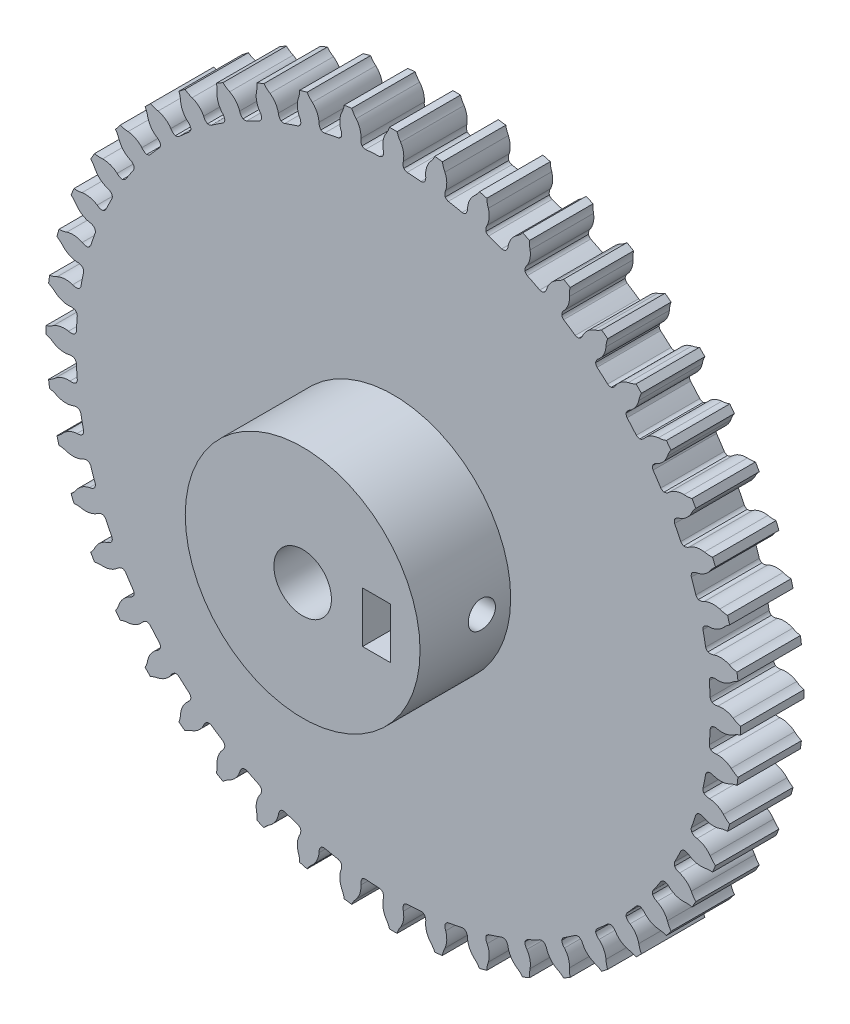
SolidWorks part; units mm, degrees
ref_plane "Front Plane" through (0, 0, 0) normal (0, 0, 1) x (1, 0, 0)
ref_plane "Top Plane" through (0, 0, 0) normal (0, 1, 0) x (1, 0, 0)
ref_plane "Right Plane" through (0, 0, 0) normal (1, 0, 0) x (0, 0, -1)
sketch "Sketch1" plane through (0, 0, 0) normal (0, 0, 1) x (1, 0, 0)
  line L0 (27.683, 56.4388) -> (28.5235, 56.4388)
  line L1 (28.5235, 56.4388) -> (28.1033, 56.4388)
  line L2 (32.6869, 56.1659) -> (33.5201, 56.0562)
  line L3 (33.5201, 56.0562) -> (33.1035, 56.1111)
  line L4 (37.6123, 55.2422) -> (38.4241, 55.0247)
  line L5 (38.4241, 55.0247) -> (38.0182, 55.1335)
  line L6 (42.375, 53.6836) -> (43.1514, 53.3619)
  line L7 (43.1514, 53.3619) -> (42.7632, 53.5227)
  line L8 (46.8935, 51.5166) -> (47.6213, 51.0964)
  line L9 (47.6213, 51.0964) -> (47.2574, 51.3065)
  line L10 (51.0905, 48.7783) -> (51.7572, 48.2667)
  line L11 (51.7572, 48.2667) -> (51.4239, 48.5225)
  line L12 (54.8942, 45.5157) -> (55.4884, 44.9214)
  line L13 (55.4884, 44.9214) -> (55.1913, 45.2186)
  line L14 (58.2394, 41.7845) -> (58.7511, 41.1177)
  line L15 (58.7511, 41.1177) -> (58.4953, 41.4511)
  line L16 (61.0691, 37.6486) -> (61.4893, 36.9207)
  line L17 (61.4893, 36.9207) -> (61.2792, 37.2847)
  line L18 (63.3347, 33.1787) -> (63.6563, 32.4022)
  line L19 (63.6563, 32.4022) -> (63.4955, 32.7905)
  line L20 (64.9974, 28.4513) -> (65.215, 27.6395)
  line L21 (65.215, 27.6395) -> (65.1062, 28.0454)
  line L22 (66.0289, 23.5474) -> (66.1386, 22.7141)
  line L23 (66.1386, 22.7141) -> (66.0838, 23.1308)
  line L24 (66.4115, 18.5507) -> (66.4115, 17.7103)
  line L25 (66.4115, 17.7103) -> (66.4115, 18.1305)
  line L26 (66.1386, 13.5469) -> (66.0289, 12.7137)
  line L27 (66.0289, 12.7137) -> (66.0838, 13.1303)
  line L28 (65.215, 8.6215) -> (64.9974, 7.8097)
  line L29 (64.9974, 7.8097) -> (65.1062, 8.2156)
  line L30 (63.6563, 3.8588) -> (63.3347, 3.0824)
  line L31 (63.3347, 3.0824) -> (63.4955, 3.4706)
  line L32 (61.4893, -0.6597) -> (61.0691, -1.3875)
  line L33 (61.0691, -1.3875) -> (61.2792, -1.0236)
  line L34 (58.7511, -4.8567) -> (58.2394, -5.5235)
  line L35 (58.2394, -5.5235) -> (58.4953, -5.1901)
  line L36 (55.4884, -8.6604) -> (54.8942, -9.2546)
  line L37 (54.8942, -9.2546) -> (55.1913, -8.9575)
  line L38 (51.7572, -12.0057) -> (51.0905, -12.5173)
  line L39 (51.0905, -12.5173) -> (51.4239, -12.2615)
  line L40 (47.6213, -14.8353) -> (46.8935, -15.2555)
  line L41 (46.8935, -15.2555) -> (47.2574, -15.0454)
  line L42 (43.1514, -17.1009) -> (42.375, -17.4225)
  line L43 (42.375, -17.4225) -> (42.7632, -17.2617)
  line L44 (38.4241, -18.7637) -> (37.6123, -18.9812)
  line L45 (37.6123, -18.9812) -> (38.0182, -18.8724)
  line L46 (33.5201, -19.7952) -> (32.6869, -19.9049)
  line L47 (32.6869, -19.9049) -> (33.1035, -19.85)
  line L48 (28.5235, -20.1777) -> (27.683, -20.1777)
  line L49 (27.683, -20.1777) -> (28.1033, -20.1777)
  line L50 (23.5196, -19.9049) -> (22.6864, -19.7952)
  line L51 (22.6864, -19.7952) -> (23.103, -19.85)
  line L52 (18.5942, -18.9812) -> (17.7825, -18.7637)
  line L53 (17.7825, -18.7637) -> (18.1883, -18.8724)
  line L54 (13.8315, -17.4225) -> (13.0551, -17.1009)
  line L55 (13.0551, -17.1009) -> (13.4433, -17.2617)
  line L56 (9.313, -15.2555) -> (8.5852, -14.8353)
  line L57 (8.5852, -14.8353) -> (8.9491, -15.0454)
  line L58 (5.116, -12.5173) -> (4.4493, -12.0057)
  line L59 (4.4493, -12.0057) -> (4.7827, -12.2615)
  line L60 (1.3124, -9.2546) -> (0.7181, -8.6604)
  line L61 (0.7181, -8.6604) -> (1.0152, -8.9575)
  line L62 (-2.0329, -5.5235) -> (-2.5445, -4.8567)
  line L63 (-2.5445, -4.8567) -> (-2.2887, -5.1901)
  line L64 (-4.8626, -1.3875) -> (-5.2828, -0.6597)
  line L65 (-5.2828, -0.6597) -> (-5.0727, -1.0236)
  line L66 (-7.1282, 3.0824) -> (-7.4498, 3.8588)
  line L67 (-7.4498, 3.8588) -> (-7.289, 3.4706)
  line L68 (-8.7909, 7.8097) -> (-9.0084, 8.6215)
  line L69 (-9.0084, 8.6215) -> (-8.8997, 8.2156)
  line L70 (-9.8224, 12.7137) -> (-9.9321, 13.5469)
  line L71 (-9.9321, 13.5469) -> (-9.8773, 13.1303)
  line L72 (-10.205, 17.7103) -> (-10.205, 18.5507)
  line L73 (-10.205, 18.5507) -> (-10.205, 18.1305)
  line L74 (-9.9321, 22.7141) -> (-9.8224, 23.5474)
  line L75 (-9.8224, 23.5474) -> (-9.8773, 23.1308)
  line L76 (-9.0084, 27.6395) -> (-8.7909, 28.4513)
  line L77 (-8.7909, 28.4513) -> (-8.8997, 28.0454)
  line L78 (-7.4498, 32.4022) -> (-7.1282, 33.1787)
  line L79 (-7.1282, 33.1787) -> (-7.289, 32.7905)
  line L80 (-5.2828, 36.9207) -> (-4.8626, 37.6486)
  line L81 (-4.8626, 37.6486) -> (-5.0727, 37.2847)
  line L82 (-2.5445, 41.1177) -> (-2.0329, 41.7845)
  line L83 (-2.0329, 41.7845) -> (-2.2887, 41.4511)
  line L84 (0.7181, 44.9214) -> (1.3124, 45.5157)
  line L85 (1.3124, 45.5157) -> (1.0152, 45.2186)
  line L86 (4.4493, 48.2667) -> (5.116, 48.7783)
  line L87 (5.116, 48.7783) -> (4.7827, 48.5225)
  line L88 (8.5852, 51.0964) -> (9.313, 51.5166)
  line L89 (9.313, 51.5166) -> (8.9491, 51.3065)
  line L90 (13.0551, 53.3619) -> (13.8315, 53.6836)
  line L91 (13.8315, 53.6836) -> (13.4433, 53.5227)
  line L92 (17.7825, 55.0247) -> (18.5942, 55.2422)
  line L93 (18.5942, 55.2422) -> (18.1883, 55.1335)
  line L94 (22.6864, 56.0562) -> (23.5196, 56.1659)
  line L95 (23.5196, 56.1659) -> (23.103, 56.1111)
  circle A1 centre (28.1033, 18.1305) radius 3.175
  circle A2 centre (28.1033, 18.1305) radius 12.9562
  arc A3 (28.5235, 56.4388) -> (28.9112, 55.6351) centre (31.0099, 57.143) ccw
  arc A4 (28.9112, 55.6351) -> (29.2209, 53.961) centre (26.9235, 54.4016) cw
  arc A5 (29.2209, 53.961) -> (29.2628, 53.2997) centre (30.05, 53.6815) ccw
  arc A7 (33.5201, 56.0562) -> (33.7996, 55.2088) centre (36.0771, 56.4298) ccw
  arc A9 (26.9856, 53.961) -> (26.9437, 53.2997) centre (26.1566, 53.6815) cw
  arc A10 (27.2953, 55.6351) -> (26.9856, 53.961) centre (29.2831, 54.4016) ccw
  arc A11 (27.683, 56.4388) -> (27.2953, 55.6351) centre (25.1967, 57.143) cw
  arc A12 (26.9437, 53.2997) -> (26.5846, 53.0976) centre (26.4555, 53.7469) cw
  arc A13 (29.2628, 53.2997) -> (29.6219, 53.0976) centre (29.751, 53.7469) ccw
  arc A14 (33.7996, 55.2088) -> (33.8882, 53.5085) centre (31.6679, 54.2453) cw
  arc A15 (33.8882, 53.5085) -> (33.8434, 52.8474) centre (34.6736, 53.1233) ccw
  arc A16 (31.6719, 53.8003) -> (31.5441, 53.1501) centre (30.8135, 53.6314) cw
  arc A17 (32.1975, 55.4197) -> (31.6719, 53.8003) centre (34.0073, 53.9373) ccw
  arc A18 (32.6869, 56.1659) -> (32.1975, 55.4197) centre (30.3137, 57.1886) cw
  arc A19 (31.5441, 53.1501) -> (31.1617, 52.9966) centre (31.1185, 53.6573) cw
  arc A20 (33.8434, 52.8474) -> (34.173, 52.6002) centre (34.3858, 53.2271) ccw
  arc A21 (38.4241, 55.0247) -> (38.5906, 54.148) centre (41.008, 55.0614) ccw
  arc A22 (38.5906, 54.148) -> (38.4565, 52.4508) centre (36.3513, 53.4711) cw
  arc A23 (38.4565, 52.4508) -> (38.3258, 51.8012) centre (39.1849, 51.9663) ccw
  arc A24 (36.2973, 53.0293) -> (36.0856, 52.4014) centre (35.4242, 52.974) cw
  arc A25 (37.0297, 54.5663) -> (36.2973, 53.0293) centre (38.6305, 52.8604) ccw
  arc A26 (37.6123, 55.2422) -> (37.0297, 54.5663) centre (35.3929, 56.5659) cw
  arc A27 (36.0856, 52.4014) -> (35.6865, 52.2991) centre (35.7299, 52.9598) cw
  arc A28 (38.3258, 51.8012) -> (38.6203, 51.513) centre (38.913, 52.1069) ccw
  arc A29 (43.1514, 53.3619) -> (43.2021, 52.471) centre (45.718, 53.061) ccw
  arc A30 (43.2021, 52.471) -> (42.8476, 50.8058) centre (40.8936, 52.0921) cw
  arc A31 (42.8476, 50.8058) -> (42.6332, 50.1788) centre (43.5065, 50.2304) ccw
  arc A32 (40.7824, 51.6612) -> (40.4906, 51.0663) centre (39.9095, 51.7203) cw
  arc A33 (41.7092, 53.0894) -> (40.7824, 51.6612) centre (43.0736, 51.1892) ccw
  arc A34 (42.375, 53.6836) -> (41.7092, 53.0894) centre (40.3473, 55.2856) cw
  arc A35 (40.4906, 51.0663) -> (40.0815, 51.017) centre (40.2108, 51.6663) cw
  arc A36 (42.6332, 50.1788) -> (42.8876, 49.8547) centre (43.2554, 50.4052) ccw
  arc A37 (47.6213, 51.0964) -> (47.5553, 50.2064) centre (50.1267, 50.463) ccw
  arc A38 (47.5553, 50.2064) -> (46.9864, 48.6017) centre (45.2171, 50.1321) cw
  arc A39 (46.9864, 48.6017) -> (46.692, 48.0081) centre (47.5646, 47.9452) ccw
  arc A40 (45.0505, 49.7194) -> (44.6836, 49.1677) centre (44.1928, 49.8919) cw
  arc A41 (46.1558, 51.0144) -> (45.0505, 49.7194) centre (47.2606, 48.9523) ccw
  arc A42 (46.8935, 51.5166) -> (46.1558, 51.0144) centre (45.0923, 53.3696) cw
  arc A43 (44.6836, 49.1677) -> (44.2716, 49.1722) centre (44.4845, 49.7991) cw
  arc A44 (46.692, 48.0081) -> (46.902, 47.6535) centre (47.3384, 48.1514) ccw
  arc A45 (51.7572, 48.2667) -> (51.5756, 47.393) centre (54.1585, 47.3118) ccw
  arc A46 (51.5756, 47.393) -> (50.8022, 45.8763) centre (49.2477, 47.6245) cw
  arc A47 (50.8022, 45.8763) -> (50.4328, 45.3262) centre (51.2897, 45.1499) ccw
  arc A48 (49.0287, 47.2371) -> (48.5929, 46.738) centre (48.2009, 47.5201) cw
  arc A49 (50.2936, 48.3767) -> (49.0287, 47.2371) centre (51.1197, 46.1881) ccw
  arc A50 (51.0905, 48.7783) -> (50.2936, 48.3767) centre (49.5466, 50.8506) cw
  arc A51 (48.5929, 46.738) -> (48.185, 46.7962) centre (48.4779, 47.39) cw
  arc A52 (50.4328, 45.3262) -> (50.5947, 44.9472) centre (51.0924, 45.3838) ccw
  arc A53 (55.4884, 44.9214) -> (55.1943, 44.0789) centre (57.7445, 43.6612) ccw
  arc A54 (55.1943, 44.0789) -> (54.2295, 42.6761) centre (52.9166, 44.6123) cw
  arc A55 (54.2295, 42.6761) -> (53.7915, 42.1789) centre (54.6181, 41.8923) ccw
  arc A56 (52.6489, 44.2568) -> (52.1517, 43.8188) centre (51.8651, 44.6454) cw
  arc A57 (54.0517, 45.2216) -> (52.6489, 44.2568) centre (54.5851, 42.9438) ccw
  arc A58 (54.8942, 45.5157) -> (54.0517, 45.2216) centre (53.634, 47.7718) cw
  arc A59 (52.1517, 43.8188) -> (51.7548, 43.9298) centre (52.1227, 44.4802) cw
  arc A60 (53.7915, 42.1789) -> (53.9025, 41.7821) centre (54.453, 42.15) ccw
  arc A61 (58.7511, 41.1177) -> (58.3495, 40.3208) centre (60.8233, 39.5738) ccw
  arc A62 (58.3495, 40.3208) -> (57.2099, 39.056) centre (56.1608, 41.147) cw
  arc A63 (57.2099, 39.056) -> (56.7107, 38.6202) centre (57.4928, 38.2282) ccw
  arc A64 (55.849, 40.8294) -> (55.2989, 40.4601) centre (55.1227, 41.317) cw
  arc A65 (57.3658, 41.6029) -> (55.849, 40.8294) centre (57.5973, 39.275) ccw
  arc A66 (58.2394, 41.7845) -> (57.3658, 41.6029) centre (57.2845, 44.1858) cw
  arc A67 (55.2989, 40.4601) -> (54.92, 40.6219) centre (55.3566, 41.1196) cw
  arc A68 (56.7107, 38.6202) -> (56.769, 38.2123) centre (57.3627, 38.5052) ccw
  arc A69 (61.4893, 36.9207) -> (60.9871, 36.1831) centre (63.3423, 35.1196) ccw
  arc A70 (60.9871, 36.1831) -> (59.6922, 35.0778) centre (58.9251, 37.2878) cw
  arc A71 (59.6922, 35.0778) -> (59.1404, 34.7109) centre (59.8647, 34.2201) ccw
  arc A72 (58.5745, 37.0137) -> (57.9809, 36.7193) centre (57.9179, 37.5919) cw
  arc A73 (60.1792, 37.5825) -> (58.5745, 37.0137) centre (60.1049, 35.2443) ccw
  arc A74 (61.0691, 37.6486) -> (60.1792, 37.5825) centre (60.4357, 40.1539) cw
  arc A75 (57.9809, 36.7193) -> (57.6263, 36.9292) centre (58.1241, 37.3657) cw
  arc A76 (59.1404, 34.7109) -> (59.1449, 34.2988) centre (59.7718, 34.5118) ccw
  arc A77 (63.6563, 32.4022) -> (63.0621, 31.7364) centre (65.2584, 30.3746) ccw
  arc A78 (63.0621, 31.7364) -> (61.634, 30.8096) centre (61.1619, 33.1009) cw
  arc A79 (61.634, 30.8096) -> (61.0391, 30.5179) centre (61.693, 29.9368) ccw
  arc A80 (60.7785, 32.8748) -> (60.1516, 32.6605) centre (60.2031, 33.5338) cw
  arc A81 (62.4438, 33.2294) -> (60.7785, 32.8748) centre (62.0649, 30.9209) ccw
  arc A82 (63.3347, 33.1787) -> (62.4438, 33.2294) centre (63.0338, 35.7453) cw
  arc A83 (60.1516, 32.6605) -> (59.8274, 32.9149) centre (60.378, 33.2826) cw
  arc A84 (61.0391, 30.5179) -> (60.9898, 30.1088) centre (61.6391, 30.238) ccw
  arc A85 (65.215, 27.6395) -> (64.539, 27.057) centre (66.5387, 25.4201) ccw
  arc A86 (64.539, 27.057) -> (63.0021, 26.3245) centre (62.8331, 28.6578) cw
  arc A87 (63.0021, 26.3245) -> (62.3742, 26.1129) centre (62.9467, 25.4514) ccw
  arc A88 (62.4235, 28.4837) -> (61.7739, 28.353) centre (61.939, 29.2122) cw
  arc A89 (64.1208, 28.6179) -> (62.4235, 28.4837) centre (63.4438, 26.3786) ccw
  arc A90 (64.9974, 28.4513) -> (64.1208, 28.6179) centre (65.0341, 31.0352) cw
  arc A91 (61.7739, 28.353) -> (61.4858, 28.6476) centre (62.0796, 28.9403) cw
  arc A92 (62.3742, 26.1129) -> (62.2719, 25.7137) centre (62.9325, 25.7571) ccw
  arc A93 (66.1386, 22.7141) -> (65.3924, 22.2248) centre (67.1613, 20.3409) ccw
  arc A94 (65.3924, 22.2248) -> (63.773, 21.6992) centre (63.9101, 24.0346) cw
  arc A95 (63.773, 21.6992) -> (63.1229, 21.5714) centre (63.6042, 20.8408) ccw
  arc A96 (63.4813, 23.9155) -> (62.8202, 23.8707) centre (63.096, 24.7009) cw
  arc A97 (65.1815, 23.8269) -> (63.4813, 23.9155) centre (64.2181, 21.6951) ccw
  arc A98 (66.0289, 23.5474) -> (65.1815, 23.8269) centre (66.4026, 26.1044) cw
  arc A99 (62.8202, 23.8707) -> (62.5729, 24.2003) centre (63.1999, 24.413) cw
  arc A100 (63.1229, 21.5714) -> (62.9694, 21.189) centre (63.63, 21.1458) ccw
  arc A101 (66.4115, 17.7103) -> (65.6078, 17.3225) centre (67.1157, 15.2239) ccw
  arc A102 (65.6078, 17.3225) -> (63.9337, 17.0128) centre (64.3744, 19.3103) cw
  arc A103 (63.9337, 17.0128) -> (63.2724, 16.971) centre (63.6542, 16.1838) ccw
  arc A104 (63.9337, 19.2482) -> (63.2724, 19.2901) centre (63.6542, 20.0772) cw
  arc A105 (65.6078, 18.9385) -> (63.9337, 19.2482) centre (64.3744, 16.9507) ccw
  arc A106 (66.4115, 18.5507) -> (65.6078, 18.9385) centre (67.1157, 21.0371) cw
  arc A107 (63.2724, 19.2901) -> (63.0703, 19.6492) centre (63.7197, 19.7782) cw
  arc A108 (63.2724, 16.971) -> (63.0703, 16.6119) centre (63.7197, 16.4828) ccw
  arc A109 (66.0289, 12.7137) -> (65.1815, 12.4341) centre (66.4026, 10.1566) ccw
  arc A110 (65.1815, 12.4341) -> (63.4813, 12.3456) centre (64.2181, 14.5659) cw
  arc A111 (63.4813, 12.3456) -> (62.8202, 12.3904) centre (63.096, 11.5601) ccw
  arc A112 (63.773, 14.5618) -> (63.1229, 14.6897) centre (63.6042, 15.4202) cw
  arc A113 (65.3924, 14.0363) -> (63.773, 14.5618) centre (63.9101, 12.2265) ccw
  arc A114 (66.1386, 13.5469) -> (65.3924, 14.0363) centre (67.1613, 15.9201) cw
  arc A115 (63.1229, 14.6897) -> (62.9694, 15.0721) centre (63.63, 15.1153) cw
  arc A116 (62.8202, 12.3904) -> (62.5729, 12.0607) centre (63.1999, 11.848) ccw
  arc A117 (64.9974, 7.8097) -> (64.1208, 7.6432) centre (65.0341, 5.2258) ccw
  arc A118 (64.1208, 7.6432) -> (62.4235, 7.7773) centre (63.4438, 9.8825) cw
  arc A119 (62.4235, 7.7773) -> (61.7739, 7.908) centre (61.939, 7.0489) ccw
  arc A120 (63.0021, 9.9365) -> (62.3742, 10.1481) centre (62.9467, 10.8096) cw
  arc A121 (64.539, 9.2041) -> (63.0021, 9.9365) centre (62.8331, 7.6033) ccw
  arc A122 (65.215, 8.6215) -> (64.539, 9.2041) centre (66.5387, 10.8409) cw
  arc A123 (62.3742, 10.1481) -> (62.2719, 10.5473) centre (62.9325, 10.5039) cw
  arc A124 (61.7739, 7.908) -> (61.4858, 7.6135) centre (62.0796, 7.3207) ccw
  arc A125 (63.3347, 3.0824) -> (62.4438, 3.0317) centre (63.0338, 0.5158) ccw
  arc A126 (62.4438, 3.0317) -> (60.7785, 3.3862) centre (62.0649, 5.3402) cw
  arc A127 (60.7785, 3.3862) -> (60.1516, 3.6006) centre (60.2031, 2.7272) ccw
  arc A128 (61.634, 5.4514) -> (61.0391, 5.7432) centre (61.693, 6.3243) cw
  arc A129 (63.0621, 4.5246) -> (61.634, 5.4514) centre (61.1619, 3.1602) ccw
  arc A130 (63.6563, 3.8588) -> (63.0621, 4.5246) centre (65.2584, 5.8864) cw
  arc A131 (61.0391, 5.7432) -> (60.9898, 6.1523) centre (61.6391, 6.023) cw
  arc A132 (60.1516, 3.6006) -> (59.8274, 3.3462) centre (60.378, 2.9784) ccw
  arc A133 (61.0691, -1.3875) -> (60.1792, -1.3215) centre (60.4357, -3.8929) ccw
  arc A134 (60.1792, -1.3215) -> (58.5745, -0.7526) centre (60.1049, 1.0167) cw
  arc A135 (58.5745, -0.7526) -> (57.9809, -0.4583) centre (57.9179, -1.3309) ccw
  arc A136 (59.6922, 1.1833) -> (59.1404, 1.5502) centre (59.8647, 2.0409) cw
  arc A137 (60.9871, 0.078) -> (59.6922, 1.1833) centre (58.9251, -1.0268) ccw
  arc A138 (61.4893, -0.6597) -> (60.9871, 0.078) centre (63.3423, 1.1415) cw
  arc A139 (59.1404, 1.5502) -> (59.1449, 1.9622) centre (59.7718, 1.7493) cw
  arc A140 (57.9809, -0.4583) -> (57.6263, -0.6682) centre (58.1241, -1.1046) ccw
  arc A141 (58.2394, -5.5235) -> (57.3658, -5.3418) centre (57.2845, -7.9247) ccw
  arc A142 (57.3658, -5.3418) -> (55.849, -4.5684) centre (57.5973, -3.0139) cw
  arc A143 (55.849, -4.5684) -> (55.2989, -4.199) centre (55.1227, -5.056) ccw
  arc A144 (57.2099, -2.7949) -> (56.7107, -2.3592) centre (57.4928, -1.9671) cw
  arc A145 (58.3495, -4.0598) -> (57.2099, -2.7949) centre (56.1608, -4.8859) ccw
  arc A146 (58.7511, -4.8567) -> (58.3495, -4.0598) centre (60.8233, -3.3128) cw
  arc A147 (56.7107, -2.3592) -> (56.769, -1.9512) centre (57.3627, -2.2441) cw
  arc A148 (55.2989, -4.199) -> (54.92, -4.3609) centre (55.3566, -4.8586) ccw
  arc A149 (54.8942, -9.2546) -> (54.0517, -8.9605) centre (53.634, -11.5107) ccw
  arc A150 (54.0517, -8.9605) -> (52.6489, -7.9957) centre (54.5851, -6.6828) cw
  arc A151 (52.6489, -7.9957) -> (52.1517, -7.5578) centre (51.8651, -8.3843) ccw
  arc A152 (54.2295, -6.4151) -> (53.7915, -5.9179) centre (54.6181, -5.6313) cw
  arc A153 (55.1943, -7.8179) -> (54.2295, -6.4151) centre (52.9166, -8.3513) ccw
  arc A154 (55.4884, -8.6604) -> (55.1943, -7.8179) centre (57.7445, -7.4002) cw
  arc A155 (53.7915, -5.9179) -> (53.9025, -5.5211) centre (54.453, -5.889) cw
  arc A156 (52.1517, -7.5578) -> (51.7548, -7.6688) centre (52.1227, -8.2192) ccw
  arc A157 (51.0905, -12.5173) -> (50.2936, -12.1157) centre (49.5466, -14.5896) ccw
  arc A158 (50.2936, -12.1157) -> (49.0287, -10.9761) centre (51.1197, -9.9271) cw
  arc A159 (49.0287, -10.9761) -> (48.5929, -10.4769) centre (48.2009, -11.259) ccw
  arc A160 (50.8022, -9.6153) -> (50.4328, -9.0651) centre (51.2897, -8.8889) cw
  arc A161 (51.5756, -11.132) -> (50.8022, -9.6153) centre (49.2477, -11.3635) ccw
  arc A162 (51.7572, -12.0057) -> (51.5756, -11.132) centre (54.1585, -11.0507) cw
  arc A163 (50.4328, -9.0651) -> (50.5947, -8.6862) centre (51.0924, -9.1228) cw
  arc A164 (48.5929, -10.4769) -> (48.185, -10.5352) centre (48.4779, -11.1289) ccw
  arc A165 (46.8935, -15.2555) -> (46.1558, -14.7534) centre (45.0923, -17.1086) ccw
  arc A166 (46.1558, -14.7534) -> (45.0505, -13.4584) centre (47.2606, -12.6913) cw
  arc A167 (45.0505, -13.4584) -> (44.6836, -12.9066) centre (44.1928, -13.6309) ccw
  arc A168 (46.9864, -12.3407) -> (46.692, -11.7471) centre (47.5646, -11.6842) cw
  arc A169 (47.5553, -13.9454) -> (46.9864, -12.3407) centre (45.2171, -13.8711) ccw
  arc A170 (47.6213, -14.8353) -> (47.5553, -13.9454) centre (50.1267, -14.202) cw
  arc A171 (46.692, -11.7471) -> (46.902, -11.3925) centre (47.3384, -11.8903) cw
  arc A172 (44.6836, -12.9066) -> (44.2716, -12.9111) centre (44.4845, -13.538) ccw
  arc A173 (42.375, -17.4225) -> (41.7092, -16.8284) centre (40.3473, -19.0246) ccw
  arc A174 (41.7092, -16.8284) -> (40.7824, -15.4002) centre (43.0736, -14.9281) cw
  arc A175 (40.7824, -15.4002) -> (40.4906, -14.8053) centre (39.9095, -15.4593) ccw
  arc A176 (42.8476, -14.5448) -> (42.6332, -13.9178) centre (43.5065, -13.9693) cw
  arc A177 (43.2021, -16.21) -> (42.8476, -14.5448) centre (40.8936, -15.8311) ccw
  arc A178 (43.1514, -17.1009) -> (43.2021, -16.21) centre (45.718, -16.8) cw
  arc A179 (42.6332, -13.9178) -> (42.8876, -13.5936) centre (43.2554, -14.1442) cw
  arc A180 (40.4906, -14.8053) -> (40.0815, -14.756) centre (40.2108, -15.4053) ccw
  arc A181 (37.6123, -18.9812) -> (37.0297, -18.3052) centre (35.3929, -20.3049) ccw
  arc A182 (37.0297, -18.3052) -> (36.2973, -16.7683) centre (38.6305, -16.5993) cw
  arc A183 (36.2973, -16.7683) -> (36.0856, -16.1404) centre (35.4242, -16.7129) ccw
  arc A184 (38.4565, -16.1897) -> (38.3258, -15.5401) centre (39.1849, -15.7052) cw
  arc A185 (38.5906, -17.887) -> (38.4565, -16.1897) centre (36.3513, -17.21) ccw
  arc A186 (38.4241, -18.7637) -> (38.5906, -17.887) centre (41.008, -18.8003) cw
  arc A187 (38.3258, -15.5401) -> (38.6203, -15.252) centre (38.913, -15.8458) cw
  arc A188 (36.0856, -16.1404) -> (35.6865, -16.0381) centre (35.7299, -16.6987) ccw
  arc A189 (32.6869, -19.9049) -> (32.1975, -19.1586) centre (30.3137, -20.9276) ccw
  arc A190 (32.1975, -19.1586) -> (31.6719, -17.5393) centre (34.0073, -17.6763) cw
  arc A191 (31.6719, -17.5393) -> (31.5441, -16.8891) centre (30.8135, -17.3704) ccw
  arc A192 (33.8882, -17.2475) -> (33.8434, -16.5864) centre (34.6736, -16.8622) cw
  arc A193 (33.7996, -18.9477) -> (33.8882, -17.2475) centre (31.6679, -17.9843) ccw
  arc A194 (33.5201, -19.7952) -> (33.7996, -18.9477) centre (36.0771, -20.1688) cw
  arc A195 (33.8434, -16.5864) -> (34.173, -16.3391) centre (34.3858, -16.9661) cw
  arc A196 (31.5441, -16.8891) -> (31.1617, -16.7356) centre (31.1185, -17.3962) ccw
  arc A197 (27.683, -20.1777) -> (27.2953, -19.374) centre (25.1967, -20.8819) ccw
  arc A198 (27.2953, -19.374) -> (26.9856, -17.6999) centre (29.2831, -18.1406) cw
  arc A199 (26.9856, -17.6999) -> (26.9437, -17.0386) centre (26.1566, -17.4204) ccw
  arc A200 (29.2209, -17.6999) -> (29.2628, -17.0386) centre (30.05, -17.4204) cw
  arc A201 (28.9112, -19.374) -> (29.2209, -17.6999) centre (26.9235, -18.1406) ccw
  arc A202 (28.5235, -20.1777) -> (28.9112, -19.374) centre (31.0099, -20.8819) cw
  arc A203 (29.2628, -17.0386) -> (29.6219, -16.8365) centre (29.751, -17.4859) cw
  arc A204 (26.9437, -17.0386) -> (26.5846, -16.8365) centre (26.4555, -17.4859) ccw
  arc A205 (22.6864, -19.7952) -> (22.4069, -18.9477) centre (20.1294, -20.1688) ccw
  arc A206 (22.4069, -18.9477) -> (22.3183, -17.2475) centre (24.5386, -17.9843) cw
  arc A207 (22.3183, -17.2475) -> (22.3631, -16.5864) centre (21.5329, -16.8622) ccw
  arc A208 (24.5346, -17.5393) -> (24.6624, -16.8891) centre (25.393, -17.3704) cw
  arc A209 (24.009, -19.1586) -> (24.5346, -17.5393) centre (22.1992, -17.6763) ccw
  arc A210 (23.5196, -19.9049) -> (24.009, -19.1586) centre (25.8928, -20.9276) cw
  arc A211 (24.6624, -16.8891) -> (25.0448, -16.7356) centre (25.088, -17.3962) cw
  arc A212 (22.3631, -16.5864) -> (22.0335, -16.3391) centre (21.8208, -16.9661) ccw
  arc A213 (17.7825, -18.7637) -> (17.6159, -17.887) centre (15.1985, -18.8003) ccw
  arc A214 (17.6159, -17.887) -> (17.7501, -16.1897) centre (19.8552, -17.21) cw
  arc A215 (17.7501, -16.1897) -> (17.8808, -15.5401) centre (17.0216, -15.7052) ccw
  arc A216 (19.9093, -16.7683) -> (20.1209, -16.1404) centre (20.7824, -16.7129) cw
  arc A217 (19.1768, -18.3052) -> (19.9093, -16.7683) centre (17.576, -16.5993) ccw
  arc A218 (18.5942, -18.9812) -> (19.1768, -18.3052) centre (20.8136, -20.3049) cw
  arc A219 (20.1209, -16.1404) -> (20.52, -16.0381) centre (20.4766, -16.6987) cw
  arc A220 (17.8808, -15.5401) -> (17.5862, -15.252) centre (17.2935, -15.8458) ccw
  arc A221 (13.0551, -17.1009) -> (13.0044, -16.21) centre (10.4885, -16.8) ccw
  arc A222 (13.0044, -16.21) -> (13.3589, -14.5448) centre (15.3129, -15.8311) cw
  arc A223 (13.3589, -14.5448) -> (13.5733, -13.9178) centre (12.7, -13.9693) ccw
  arc A224 (15.4242, -15.4002) -> (15.7159, -14.8053) centre (16.297, -15.4593) cw
  arc A225 (14.4974, -16.8284) -> (15.4242, -15.4002) centre (13.1329, -14.9281) ccw
  arc A226 (13.8315, -17.4225) -> (14.4974, -16.8284) centre (15.8592, -19.0246) cw
  arc A227 (15.7159, -14.8053) -> (16.125, -14.756) centre (15.9957, -15.4053) cw
  arc A228 (13.5733, -13.9178) -> (13.3189, -13.5936) centre (12.9512, -14.1442) ccw
  arc A229 (8.5852, -14.8353) -> (8.6513, -13.9454) centre (6.0798, -14.202) ccw
  arc A230 (8.6513, -13.9454) -> (9.2201, -12.3407) centre (10.9894, -13.8711) cw
  arc A231 (9.2201, -12.3407) -> (9.5145, -11.7471) centre (8.6419, -11.6842) ccw
  arc A232 (11.156, -13.4584) -> (11.5229, -12.9066) centre (12.0137, -13.6309) cw
  arc A233 (10.0507, -14.7534) -> (11.156, -13.4584) centre (8.946, -12.6913) ccw
  arc A234 (9.313, -15.2555) -> (10.0507, -14.7534) centre (11.1142, -17.1086) cw
  arc A235 (11.5229, -12.9066) -> (11.9349, -12.9111) centre (11.722, -13.538) cw
  arc A236 (9.5145, -11.7471) -> (9.3045, -11.3925) centre (8.8681, -11.8903) ccw
  arc A237 (4.4493, -12.0057) -> (4.6309, -11.132) centre (2.048, -11.0507) ccw
  arc A238 (4.6309, -11.132) -> (5.4044, -9.6153) centre (6.9588, -11.3635) cw
  arc A239 (5.4044, -9.6153) -> (5.7737, -9.0651) centre (4.9168, -8.8889) ccw
  arc A240 (7.1778, -10.9761) -> (7.6136, -10.4769) centre (8.0056, -11.259) cw
  arc A241 (5.9129, -12.1157) -> (7.1778, -10.9761) centre (5.0868, -9.9271) ccw
  arc A242 (5.116, -12.5173) -> (5.9129, -12.1157) centre (6.6599, -14.5896) cw
  arc A243 (7.6136, -10.4769) -> (8.0215, -10.5352) centre (7.7286, -11.1289) cw
  arc A244 (5.7737, -9.0651) -> (5.6118, -8.6862) centre (5.1141, -9.1228) ccw
  arc A245 (0.7181, -8.6604) -> (1.0122, -7.8179) centre (-1.538, -7.4002) ccw
  arc A246 (1.0122, -7.8179) -> (1.977, -6.4151) centre (3.29, -8.3513) cw
  arc A247 (1.977, -6.4151) -> (2.415, -5.9179) centre (1.5884, -5.6313) ccw
  arc A248 (3.5576, -7.9957) -> (4.0549, -7.5578) centre (4.3415, -8.3843) cw
  arc A249 (2.1549, -8.9605) -> (3.5576, -7.9957) centre (1.6215, -6.6828) ccw
  arc A250 (1.3124, -9.2546) -> (2.1549, -8.9605) centre (2.5726, -11.5107) cw
  arc A251 (4.0549, -7.5578) -> (4.4517, -7.6688) centre (4.0838, -8.2192) cw
  arc A252 (2.415, -5.9179) -> (2.304, -5.5211) centre (1.7535, -5.889) ccw
  arc A253 (-2.5445, -4.8567) -> (-2.143, -4.0598) centre (-4.6168, -3.3128) ccw
  arc A254 (-2.143, -4.0598) -> (-1.0033, -2.7949) centre (0.0457, -4.8859) cw
  arc A255 (-1.0033, -2.7949) -> (-0.5042, -2.3592) centre (-1.2863, -1.9671) ccw
  arc A256 (0.3575, -4.5684) -> (0.9076, -4.199) centre (1.0839, -5.056) cw
  arc A257 (-1.1592, -5.3418) -> (0.3575, -4.5684) centre (-1.3908, -3.0139) ccw
  arc A258 (-2.0329, -5.5235) -> (-1.1592, -5.3418) centre (-1.078, -7.9247) cw
  arc A259 (0.9076, -4.199) -> (1.2865, -4.3609) centre (0.8499, -4.8586) cw
  arc A260 (-0.5042, -2.3592) -> (-0.5625, -1.9512) centre (-1.1562, -2.2441) ccw
  arc A261 (-5.2828, -0.6597) -> (-4.7806, 0.078) centre (-7.1358, 1.1415) ccw
  arc A262 (-4.7806, 0.078) -> (-3.4856, 1.1833) centre (-2.7185, -1.0268) cw
  arc A263 (-3.4856, 1.1833) -> (-2.9339, 1.5502) centre (-3.6581, 2.0409) ccw
  arc A264 (-2.368, -0.7526) -> (-1.7743, -0.4583) centre (-1.7114, -1.3309) cw
  arc A265 (-3.9727, -1.3215) -> (-2.368, -0.7526) centre (-3.8983, 1.0167) ccw
  arc A266 (-4.8626, -1.3875) -> (-3.9727, -1.3215) centre (-4.2292, -3.8929) cw
  arc A267 (-1.7743, -0.4583) -> (-1.4198, -0.6682) centre (-1.9176, -1.1046) cw
  arc A268 (-2.9339, 1.5502) -> (-2.9384, 1.9622) centre (-3.5653, 1.7493) ccw
  arc A269 (-7.4498, 3.8588) -> (-6.8556, 4.5246) centre (-9.0519, 5.8864) ccw
  arc A270 (-6.8556, 4.5246) -> (-5.4275, 5.4514) centre (-4.9554, 3.1602) cw
  arc A271 (-5.4275, 5.4514) -> (-4.8325, 5.7432) centre (-5.4865, 6.3243) ccw
  arc A272 (-4.572, 3.3862) -> (-3.9451, 3.6006) centre (-3.9966, 2.7272) cw
  arc A273 (-6.2372, 3.0317) -> (-4.572, 3.3862) centre (-5.8584, 5.3402) ccw
  arc A274 (-7.1282, 3.0824) -> (-6.2372, 3.0317) centre (-6.8272, 0.5158) cw
  arc A275 (-3.9451, 3.6006) -> (-3.6209, 3.3462) centre (-4.1714, 2.9784) cw
  arc A276 (-4.8325, 5.7432) -> (-4.7832, 6.1523) centre (-5.4326, 6.023) ccw
  arc A277 (-9.0084, 8.6215) -> (-8.3325, 9.2041) centre (-10.3322, 10.8409) ccw
  arc A278 (-8.3325, 9.2041) -> (-6.7956, 9.9365) centre (-6.6266, 7.6033) cw
  arc A279 (-6.7956, 9.9365) -> (-6.1677, 10.1481) centre (-6.7402, 10.8096) ccw
  arc A280 (-6.217, 7.7773) -> (-5.5674, 7.908) centre (-5.7325, 7.0489) cw
  arc A281 (-7.9142, 7.6432) -> (-6.217, 7.7773) centre (-7.2373, 9.8825) ccw
  arc A282 (-8.7909, 7.8097) -> (-7.9142, 7.6432) centre (-8.8276, 5.2258) cw
  arc A283 (-5.5674, 7.908) -> (-5.2792, 7.6135) centre (-5.8731, 7.3207) cw
  arc A284 (-6.1677, 10.1481) -> (-6.0654, 10.5473) centre (-6.726, 10.5039) ccw
  arc A285 (-9.9321, 13.5469) -> (-9.1859, 14.0363) centre (-10.9548, 15.9201) ccw
  arc A286 (-9.1859, 14.0363) -> (-7.5665, 14.5618) centre (-7.7035, 12.2265) cw
  arc A287 (-7.5665, 14.5618) -> (-6.9164, 14.6897) centre (-7.3977, 15.4202) ccw
  arc A288 (-7.2748, 12.3456) -> (-6.6137, 12.3904) centre (-6.8895, 11.5601) cw
  arc A289 (-8.975, 12.4341) -> (-7.2748, 12.3456) centre (-8.0115, 14.5659) ccw
  arc A290 (-9.8224, 12.7137) -> (-8.975, 12.4341) centre (-10.1961, 10.1566) cw
  arc A291 (-6.6137, 12.3904) -> (-6.3664, 12.0607) centre (-6.9934, 11.848) cw
  arc A292 (-6.9164, 14.6897) -> (-6.7629, 15.0721) centre (-7.4235, 15.1153) ccw
  arc A293 (-10.205, 18.5507) -> (-9.4013, 18.9385) centre (-10.9092, 21.0371) ccw
  arc A294 (-9.4013, 18.9385) -> (-7.7272, 19.2482) centre (-8.1678, 16.9507) cw
  arc A295 (-7.7272, 19.2482) -> (-7.0659, 19.2901) centre (-7.4477, 20.0772) ccw
  arc A296 (-7.7272, 17.0128) -> (-7.0659, 16.971) centre (-7.4477, 16.1838) cw
  arc A297 (-9.4013, 17.3225) -> (-7.7272, 17.0128) centre (-8.1678, 19.3103) ccw
  arc A298 (-10.205, 17.7103) -> (-9.4013, 17.3225) centre (-10.9092, 15.2239) cw
  arc A299 (-7.0659, 16.971) -> (-6.8638, 16.6119) centre (-7.5131, 16.4828) cw
  arc A300 (-7.0659, 19.2901) -> (-6.8638, 19.6492) centre (-7.5131, 19.7782) ccw
  arc A301 (-9.8224, 23.5474) -> (-8.975, 23.8269) centre (-10.1961, 26.1044) ccw
  arc A302 (-8.975, 23.8269) -> (-7.2748, 23.9155) centre (-8.0115, 21.6951) cw
  arc A303 (-7.2748, 23.9155) -> (-6.6137, 23.8707) centre (-6.8895, 24.7009) ccw
  arc A304 (-7.5665, 21.6992) -> (-6.9164, 21.5714) centre (-7.3977, 20.8408) cw
  arc A305 (-9.1859, 22.2248) -> (-7.5665, 21.6992) centre (-7.7035, 24.0346) ccw
  arc A306 (-9.9321, 22.7141) -> (-9.1859, 22.2248) centre (-10.9548, 20.3409) cw
  arc A307 (-6.9164, 21.5714) -> (-6.7629, 21.189) centre (-7.4235, 21.1458) cw
  arc A308 (-6.6137, 23.8707) -> (-6.3664, 24.2003) centre (-6.9934, 24.413) ccw
  arc A309 (-8.7909, 28.4513) -> (-7.9142, 28.6179) centre (-8.8276, 31.0352) ccw
  arc A310 (-7.9142, 28.6179) -> (-6.217, 28.4837) centre (-7.2373, 26.3786) cw
  arc A311 (-6.217, 28.4837) -> (-5.5674, 28.353) centre (-5.7325, 29.2122) ccw
  arc A312 (-6.7956, 26.3245) -> (-6.1677, 26.1129) centre (-6.7402, 25.4514) cw
  arc A313 (-8.3325, 27.057) -> (-6.7956, 26.3245) centre (-6.6266, 28.6578) ccw
  arc A314 (-9.0084, 27.6395) -> (-8.3325, 27.057) centre (-10.3322, 25.4201) cw
  arc A315 (-6.1677, 26.1129) -> (-6.0654, 25.7137) centre (-6.726, 25.7571) cw
  arc A316 (-5.5674, 28.353) -> (-5.2792, 28.6476) centre (-5.8731, 28.9403) ccw
  arc A317 (-7.1282, 33.1787) -> (-6.2372, 33.2294) centre (-6.8272, 35.7453) ccw
  arc A318 (-6.2372, 33.2294) -> (-4.572, 32.8748) centre (-5.8584, 30.9209) cw
  arc A319 (-4.572, 32.8748) -> (-3.9451, 32.6605) centre (-3.9966, 33.5338) ccw
  arc A320 (-5.4275, 30.8096) -> (-4.8325, 30.5179) centre (-5.4865, 29.9368) cw
  arc A321 (-6.8556, 31.7364) -> (-5.4275, 30.8096) centre (-4.9554, 33.1009) ccw
  arc A322 (-7.4498, 32.4022) -> (-6.8556, 31.7364) centre (-9.0519, 30.3746) cw
  arc A323 (-4.8325, 30.5179) -> (-4.7832, 30.1088) centre (-5.4326, 30.238) cw
  arc A324 (-3.9451, 32.6605) -> (-3.6209, 32.9149) centre (-4.1714, 33.2826) ccw
  arc A325 (-4.8626, 37.6486) -> (-3.9727, 37.5825) centre (-4.2292, 40.1539) ccw
  arc A326 (-3.9727, 37.5825) -> (-2.368, 37.0137) centre (-3.8983, 35.2443) cw
  arc A327 (-2.368, 37.0137) -> (-1.7743, 36.7193) centre (-1.7114, 37.5919) ccw
  arc A328 (-3.4856, 35.0778) -> (-2.9339, 34.7109) centre (-3.6581, 34.2201) cw
  arc A329 (-4.7806, 36.1831) -> (-3.4856, 35.0778) centre (-2.7185, 37.2878) ccw
  arc A330 (-5.2828, 36.9207) -> (-4.7806, 36.1831) centre (-7.1358, 35.1196) cw
  arc A331 (-2.9339, 34.7109) -> (-2.9384, 34.2988) centre (-3.5653, 34.5118) cw
  arc A332 (-1.7743, 36.7193) -> (-1.4198, 36.9292) centre (-1.9176, 37.3657) ccw
  arc A333 (-2.0329, 41.7845) -> (-1.1592, 41.6029) centre (-1.078, 44.1858) ccw
  arc A334 (-1.1592, 41.6029) -> (0.3575, 40.8294) centre (-1.3908, 39.275) cw
  arc A335 (0.3575, 40.8294) -> (0.9076, 40.4601) centre (1.0839, 41.317) ccw
  arc A336 (-1.0033, 39.056) -> (-0.5042, 38.6202) centre (-1.2863, 38.2282) cw
  arc A337 (-2.143, 40.3208) -> (-1.0033, 39.056) centre (0.0457, 41.147) ccw
  arc A338 (-2.5445, 41.1177) -> (-2.143, 40.3208) centre (-4.6168, 39.5738) cw
  arc A339 (-0.5042, 38.6202) -> (-0.5625, 38.2123) centre (-1.1562, 38.5052) cw
  arc A340 (0.9076, 40.4601) -> (1.2865, 40.6219) centre (0.8499, 41.1196) ccw
  arc A341 (1.3124, 45.5157) -> (2.1549, 45.2216) centre (2.5726, 47.7718) ccw
  arc A342 (2.1549, 45.2216) -> (3.5576, 44.2568) centre (1.6215, 42.9438) cw
  arc A343 (3.5576, 44.2568) -> (4.0549, 43.8188) centre (4.3415, 44.6454) ccw
  arc A344 (1.977, 42.6761) -> (2.415, 42.1789) centre (1.5884, 41.8923) cw
  arc A345 (1.0122, 44.0789) -> (1.977, 42.6761) centre (3.29, 44.6123) ccw
  arc A346 (0.7181, 44.9214) -> (1.0122, 44.0789) centre (-1.538, 43.6612) cw
  arc A347 (2.415, 42.1789) -> (2.304, 41.7821) centre (1.7535, 42.15) cw
  arc A348 (4.0549, 43.8188) -> (4.4517, 43.9298) centre (4.0838, 44.4802) ccw
  arc A349 (5.116, 48.7783) -> (5.9129, 48.3767) centre (6.6599, 50.8506) ccw
  arc A350 (5.9129, 48.3767) -> (7.1778, 47.2371) centre (5.0868, 46.1881) cw
  arc A351 (7.1778, 47.2371) -> (7.6136, 46.738) centre (8.0056, 47.5201) ccw
  arc A352 (5.4044, 45.8763) -> (5.7737, 45.3262) centre (4.9168, 45.1499) cw
  arc A353 (4.6309, 47.393) -> (5.4044, 45.8763) centre (6.9588, 47.6245) ccw
  arc A354 (4.4493, 48.2667) -> (4.6309, 47.393) centre (2.048, 47.3118) cw
  arc A355 (5.7737, 45.3262) -> (5.6118, 44.9472) centre (5.1141, 45.3838) cw
  arc A356 (7.6136, 46.738) -> (8.0215, 46.7962) centre (7.7286, 47.39) ccw
  arc A357 (9.313, 51.5166) -> (10.0507, 51.0144) centre (11.1142, 53.3696) ccw
  arc A358 (10.0507, 51.0144) -> (11.156, 49.7194) centre (8.946, 48.9523) cw
  arc A359 (11.156, 49.7194) -> (11.5229, 49.1677) centre (12.0137, 49.8919) ccw
  arc A360 (9.2201, 48.6017) -> (9.5145, 48.0081) centre (8.6419, 47.9452) cw
  arc A361 (8.6513, 50.2064) -> (9.2201, 48.6017) centre (10.9894, 50.1321) ccw
  arc A362 (8.5852, 51.0964) -> (8.6513, 50.2064) centre (6.0798, 50.463) cw
  arc A363 (9.5145, 48.0081) -> (9.3045, 47.6535) centre (8.8681, 48.1514) cw
  arc A364 (11.5229, 49.1677) -> (11.9349, 49.1722) centre (11.722, 49.7991) ccw
  arc A365 (13.8315, 53.6836) -> (14.4974, 53.0894) centre (15.8592, 55.2856) ccw
  arc A366 (14.4974, 53.0894) -> (15.4242, 51.6612) centre (13.1329, 51.1892) cw
  arc A367 (15.4242, 51.6612) -> (15.7159, 51.0663) centre (16.297, 51.7203) ccw
  arc A368 (13.3589, 50.8058) -> (13.5733, 50.1788) centre (12.7, 50.2304) cw
  arc A369 (13.0044, 52.471) -> (13.3589, 50.8058) centre (15.3129, 52.0921) ccw
  arc A370 (13.0551, 53.3619) -> (13.0044, 52.471) centre (10.4885, 53.061) cw
  arc A371 (13.5733, 50.1788) -> (13.3189, 49.8547) centre (12.9512, 50.4052) cw
  arc A372 (15.7159, 51.0663) -> (16.125, 51.017) centre (15.9957, 51.6663) ccw
  arc A373 (18.5942, 55.2422) -> (19.1768, 54.5663) centre (20.8136, 56.5659) ccw
  arc A374 (19.1768, 54.5663) -> (19.9093, 53.0293) centre (17.576, 52.8604) cw
  arc A375 (19.9093, 53.0293) -> (20.1209, 52.4014) centre (20.7824, 52.974) ccw
  arc A376 (17.7501, 52.4508) -> (17.8808, 51.8012) centre (17.0216, 51.9663) cw
  arc A377 (17.6159, 54.148) -> (17.7501, 52.4508) centre (19.8552, 53.4711) ccw
  arc A378 (17.7825, 55.0247) -> (17.6159, 54.148) centre (15.1985, 55.0614) cw
  arc A379 (17.8808, 51.8012) -> (17.5862, 51.513) centre (17.2935, 52.1069) cw
  arc A380 (20.1209, 52.4014) -> (20.52, 52.2991) centre (20.4766, 52.9598) ccw
  arc A381 (23.5196, 56.1659) -> (24.009, 55.4197) centre (25.8928, 57.1886) ccw
  arc A382 (24.009, 55.4197) -> (24.5346, 53.8003) centre (22.1992, 53.9373) cw
  arc A383 (24.5346, 53.8003) -> (24.6624, 53.1501) centre (25.393, 53.6314) ccw
  arc A384 (22.3183, 53.5085) -> (22.3631, 52.8474) centre (21.5329, 53.1233) cw
  arc A385 (22.4069, 55.2088) -> (22.3183, 53.5085) centre (24.5386, 54.2453) ccw
  arc A386 (22.6864, 56.0562) -> (22.4069, 55.2088) centre (20.1294, 56.4298) cw
  arc A387 (22.3631, 52.8474) -> (22.0335, 52.6002) centre (21.8208, 53.2271) cw
  arc A388 (24.6624, 53.1501) -> (25.0448, 52.9966) centre (25.088, 53.6573) ccw
  arc A389 (9.3045, 47.6535) -> (8.0215, 46.7962) centre (28.1033, 18.1305) ccw
  arc A390 (13.3189, 49.8547) -> (11.9349, 49.1722) centre (28.1033, 18.1305) ccw
  arc A391 (17.5862, 51.513) -> (16.125, 51.017) centre (28.1033, 18.1305) ccw
  arc A392 (22.0335, 52.6002) -> (20.52, 52.2991) centre (28.1033, 18.1305) ccw
  arc A393 (26.5846, 53.0976) -> (25.0448, 52.9966) centre (28.1033, 18.1305) ccw
  arc A394 (31.1617, 52.9966) -> (29.6219, 53.0976) centre (28.1033, 18.1305) ccw
  arc A395 (35.6865, 52.2991) -> (34.173, 52.6002) centre (28.1033, 18.1305) ccw
  arc A396 (40.0815, 51.017) -> (38.6203, 51.513) centre (28.1033, 18.1305) ccw
  arc A397 (44.2716, 49.1722) -> (42.8876, 49.8547) centre (28.1033, 18.1305) ccw
  arc A398 (48.185, 46.7962) -> (46.902, 47.6535) centre (28.1033, 18.1305) ccw
  arc A399 (51.7548, 43.9298) -> (50.5947, 44.9472) centre (28.1033, 18.1305) ccw
  arc A400 (54.92, 40.6219) -> (53.9025, 41.7821) centre (28.1033, 18.1305) ccw
  arc A401 (57.6263, 36.9292) -> (56.769, 38.2123) centre (28.1033, 18.1305) ccw
  arc A402 (59.8274, 32.9149) -> (59.1449, 34.2988) centre (28.1033, 18.1305) ccw
  arc A403 (61.4858, 28.6476) -> (60.9898, 30.1088) centre (28.1033, 18.1305) ccw
  arc A404 (62.5729, 24.2003) -> (62.2719, 25.7137) centre (28.1033, 18.1305) ccw
  arc A405 (63.0703, 19.6492) -> (62.9694, 21.189) centre (28.1033, 18.1305) ccw
  arc A406 (62.9694, 15.0721) -> (63.0703, 16.6119) centre (28.1033, 18.1305) ccw
  arc A407 (62.2719, 10.5473) -> (62.5729, 12.0607) centre (28.1033, 18.1305) ccw
  arc A408 (60.9898, 6.1523) -> (61.4858, 7.6135) centre (28.1033, 18.1305) ccw
  arc A409 (59.1449, 1.9622) -> (59.8274, 3.3462) centre (28.1033, 18.1305) ccw
  arc A410 (56.769, -1.9512) -> (57.6263, -0.6682) centre (28.1033, 18.1305) ccw
  arc A411 (53.9025, -5.5211) -> (54.92, -4.3609) centre (28.1033, 18.1305) ccw
  arc A412 (50.5947, -8.6862) -> (51.7548, -7.6688) centre (28.1033, 18.1305) ccw
  arc A413 (46.902, -11.3925) -> (48.185, -10.5352) centre (28.1033, 18.1305) ccw
  arc A414 (42.8876, -13.5936) -> (44.2716, -12.9111) centre (28.1033, 18.1305) ccw
  arc A415 (38.6203, -15.252) -> (40.0815, -14.756) centre (28.1033, 18.1305) ccw
  arc A416 (34.173, -16.3391) -> (35.6865, -16.0381) centre (28.1033, 18.1305) ccw
  arc A417 (29.6219, -16.8365) -> (31.1617, -16.7356) centre (28.1033, 18.1305) ccw
  arc A418 (25.0448, -16.7356) -> (26.5846, -16.8365) centre (28.1033, 18.1305) ccw
  arc A419 (20.52, -16.0381) -> (22.0335, -16.3391) centre (28.1033, 18.1305) ccw
  arc A420 (16.125, -14.756) -> (17.5862, -15.252) centre (28.1033, 18.1305) ccw
  arc A421 (11.9349, -12.9111) -> (13.3189, -13.5936) centre (28.1033, 18.1305) ccw
  arc A422 (8.0215, -10.5352) -> (9.3045, -11.3925) centre (28.1033, 18.1305) ccw
  arc A423 (4.4517, -7.6688) -> (5.6118, -8.6862) centre (28.1033, 18.1305) ccw
  arc A424 (1.2865, -4.3609) -> (2.304, -5.5211) centre (28.1033, 18.1305) ccw
  arc A425 (-1.4198, -0.6682) -> (-0.5625, -1.9512) centre (28.1033, 18.1305) ccw
  arc A426 (-3.6209, 3.3462) -> (-2.9384, 1.9622) centre (28.1033, 18.1305) ccw
  arc A427 (-5.2792, 7.6135) -> (-4.7832, 6.1523) centre (28.1033, 18.1305) ccw
  arc A428 (-6.3664, 12.0607) -> (-6.0654, 10.5473) centre (28.1033, 18.1305) ccw
  arc A429 (-6.8638, 16.6119) -> (-6.7629, 15.0721) centre (28.1033, 18.1305) ccw
  arc A430 (-6.7629, 21.189) -> (-6.8638, 19.6492) centre (28.1033, 18.1305) ccw
  arc A431 (-6.0654, 25.7137) -> (-6.3664, 24.2003) centre (28.1033, 18.1305) ccw
  arc A432 (-4.7832, 30.1088) -> (-5.2792, 28.6476) centre (28.1033, 18.1305) ccw
  arc A433 (-2.9384, 34.2988) -> (-3.6209, 32.9149) centre (28.1033, 18.1305) ccw
  arc A434 (-0.5625, 38.2123) -> (-1.4198, 36.9292) centre (28.1033, 18.1305) ccw
  arc A435 (2.304, 41.7821) -> (1.2865, 40.6219) centre (28.1033, 18.1305) ccw
  arc A436 (5.6118, 44.9472) -> (4.4517, 43.9298) centre (28.1033, 18.1305) ccw
  point P917 (28.1033, 18.1305)
  dimension "D1" = 6.35
  dimension "D2" = 48
extrude "Boss-Extrude1" add sketch "Sketch1" along normal blind 7 contours A2 | A2 A1 region at (27.8932, 55.3553, 0) region at (15.5135, 18.1305, 0)
extrude "Boss-Extrude2" add sketch "Sketch1<3>" along normal blind 17 contours A2 A1 region at (15.5135, 18.1305, 0)
sketch "Sketch1<3>" plane through (0, 0, 0) normal (0, 0, 1) x (1, 0, 0) same geometry as "Sketch1"
sketch "Sketch2" plane through (0, 0, 17) normal (0, 0, 1) x (1, 0, 0)
  line L2 (34.7128, 20.9305) -> (37.8128, 20.9305)
  line L3 (34.7128, 20.9305) -> (34.7128, 15.3305)
  line L4 (34.7128, 15.3305) -> (37.8128, 15.3305)
  line L5 (37.8128, 20.9305) -> (37.8128, 15.3305)
  line L6 (34.7128, 20.9305) -> (37.8128, 15.3305) construction
  line L7 (34.7128, 15.3305) -> (37.8128, 20.9305) construction
  point P7 (36.2628, 18.1305)
  dimension "D1" = 3.1
  dimension "D2" = 5.6
extrude "Cut-Extrude1" cut sketch "Sketch2" against normal blind 8.5
sketch "Sketch3" plane through (34.7128, 0, 0) normal (1, 0, 0) x (0, 0, -1)
  line L0 (-8.5, 18.1305) -> (-8.5637, 18.1305)
  line L1 (-8.5, 15.3305) -> (-8.5, 20.9305) construction
  line L2 (-8.5, 20.9305) -> (-8.5637, 20.9305)
  line L3 (-6.9471, 18.1305) -> (-8.5637, 20.9305)
  line L8 (-8.5637, 15.3305) -> (-6.9471, 18.1305)
  line L10 (-8.5637, 20.9305) -> (-8.5637, 15.3305)
  line L12 (-11.7968, 15.3305) -> (-10.1802, 15.3305) [skipped]
  line L13 (-13.4134, 18.1305) -> (-12.6051, 16.7305) [skipped]
  line L14 (-11.7968, 20.9305) -> (-12.6051, 19.5305) [skipped]
  line L15 (-8.5637, 20.9305) -> (-10.1802, 20.9305) [skipped]
  line M8 (-8.5, 15.3305) -> (-8.5, 20.9305)
extrude "Cut-Extrude2" cut sketch "Sketch3" along normal blind 3.1 contours L8 L3 M8 region at (34.7128, 18.1305, 7.9824)
sketch "Sketch4" plane through (34.7128, 0, 0) normal (1, 0, 0) x (0, 0, -1)
  circle A1 centre (-10.1802, 18.1305) radius 1.5
  dimension "D2" = 3
extrude "Cut-Extrude3" cut sketch "Sketch4" along normal blind 11.1
